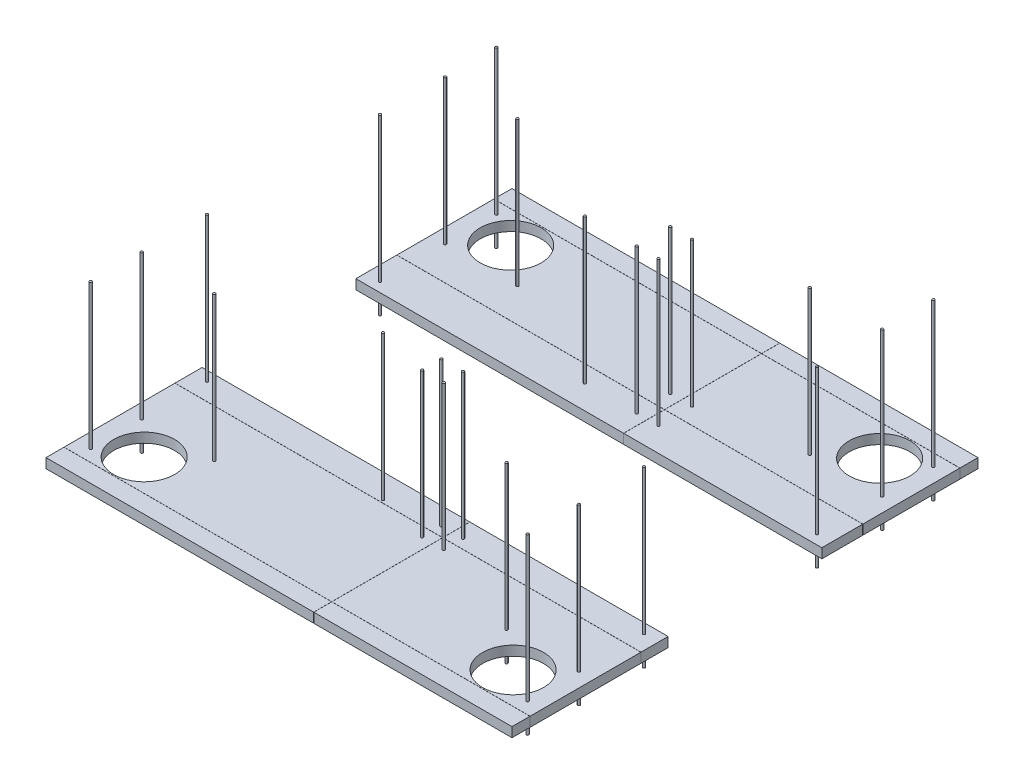
SolidWorks part; units mm, degrees
ref_plane "Front" through (0, 0, 0) normal (0, 0, 1) x (1, 0, 0)
ref_plane "Top" through (0, 0, 0) normal (0, 1, 0) x (1, 0, 0)
ref_plane "Right" through (0, 0, 0) normal (1, 0, 0) x (0, 0, -1)
sketch "Sketch1" plane through (0, 0, 0) normal (0, 1, 0) x (1, 0, 0)
  line L1 (-2454.275, 2454.275) -> (2454.275, 2454.275)
  line L2 (-2454.275, 2454.275) -> (-2454.275, -2454.275)
  line L3 (-2454.275, -2454.275) -> (2454.275, -2454.275)
  line L4 (2454.275, 2454.275) -> (2454.275, -2454.275)
  line L5 (-2454.275, 2454.275) -> (2454.275, -2454.275) construction
  line L6 (-2454.275, -2454.275) -> (2454.275, 2454.275) construction
  point P0 (0, 0)
  dimension "D1" = 4908.55
  dimension "D2" = 4908.55
extrude "Boss-Extrude1" add sketch "Sketch1" along normal blind 101.6
sketch "Sketch2" plane through (0, 101.6, 0) normal (0, 1, 0) x (1, 0, 0)
  line L0 (-2454.275, 2454.275) -> (-2454.275, -2454.275) construction
  line L1 (2454.275, -809.625) -> (-2454.275, -809.625)
  line L2 (2454.275, -809.625) -> (2454.275, 809.625)
  line L3 (2454.275, 809.625) -> (-2454.275, 809.625)
  line L4 (-2454.275, -809.625) -> (-2454.275, 809.625)
  line L5 (2454.275, -809.625) -> (-2454.275, 809.625) construction
  line L6 (2454.275, 809.625) -> (-2454.275, -809.625) construction
  point P0 (0, 0)
  dimension "D1" = 1619.25
extrude "Cut-Extrude1" cut sketch "Sketch2" against normal through all
sketch "Sketch4" plane through (0, 101.6, 0) normal (0, 1, 0) x (1, 0, 0)
  line L0 (-2454.275, -2263.775) -> (2454.275, -2263.775)
  line L3 (-2454.275, -2454.275) -> (2454.275, -2454.275) construction
  line L4 (-2454.275, -1095.375) -> (2454.275, -1095.375)
  line L5 (-2454.275, -809.625) -> (-2454.275, -2454.275) construction
  line L6 (-2454.275, -809.625) -> (2454.275, -809.625) construction
  line L7 (-2454.275, 2263.775) -> (2454.275, 2263.775)
  line L10 (-2454.275, 1241.425) -> (2454.275, 1241.425)
  line L11 (-2454.275, 2454.275) -> (-2454.275, 809.625) construction
  line L12 (2454.275, 809.625) -> (2454.275, 2454.275) construction
  line L13 (2454.275, 2454.275) -> (-2454.275, 2454.275) construction
  line L14 (2454.275, 809.625) -> (-2454.275, 809.625) construction
  line L15 (-2454.275, -1095.375) -> (-2454.275, -2263.775) construction
  line L16 (2454.275, -1095.375) -> (2454.275, -2263.775) construction
  line L17 (2454.275, 1241.425) -> (2454.275, 2263.775) construction
  line L18 (-2454.275, 1241.425) -> (-2454.275, 2263.775) construction
  line L19 (2454.275, -2454.275) -> (2454.275, -809.625) construction
  dimension "D1" = 190.5
  dimension "D2" = 1168.4
  dimension "D3" = 285.75
  dimension "D4" = 190.5
  dimension "D5" = 1022.35
  dimension "D6" = 431.8
extrude "Cut-Extrude-Thin1" cut sketch "Sketch4" against normal through all thin thin type one direction wall 1.27
sketch "Sketch5" plane through (0, 101.6, 0) normal (0, 1, 0) x (1, 0, 0)
  line L0 (365.125, -2454.275) -> (365.125, 2454.275)
  line L1 (-2454.275, -2454.275) -> (2454.275, -2454.275) construction
  line L2 (2454.275, 2454.275) -> (-2454.275, 2454.275) construction
  line L3 (2454.275, -2263.775) -> (2454.275, -1096.645) construction
  line L4 (-2454.275, -1096.645) -> (-2454.275, -2263.775) construction
  dimension "D1" = 2089.15
  dimension "D2" = 2819.4
extrude "Cut-Extrude-Thin2" cut sketch "Sketch5" against normal through all and the other way through all thin thin type one direction wall 1.27
sketch "Sketch8" plane through (0, 101.6, 0) normal (0, 1, 0) x (1, 0, 0)
  line L0 (-974.0807, 502.3386) -> (-974.0807, 1597.0052) construction
sketch "Sketch6" plane through (0, 101.6, 0) normal (0, 1, 0) x (1, 0, 0)
  line L0 (1943.1, 1929.13) -> (1943.1, 2262.505) construction
  line L1 (-1943.1, 1929.13) -> (1943.1, 1929.13) construction
  line L2 (-1943.1, 1929.13) -> (-1943.1, -1931.67) construction
  line L3 (-1943.1, -1931.67) -> (1943.1, -1931.67) construction
  line L4 (1943.1, 1929.13) -> (1943.1, -1931.67) construction
  line L5 (-1943.1, -1931.67) -> (-1943.1, -2265.045) construction
  line L6 (-2454.275, -2265.045) -> (365.125, -2265.045) construction
  line L7 (366.395, 2262.505) -> (2454.275, 2262.505) construction
  line L9 (2454.275, 1241.425) -> (2454.275, 2262.505) construction
  line L11 (-2454.275, -1096.645) -> (-2454.275, -2263.775) construction
  circle A0 centre (1943.1, 1929.13) radius 320.675
  circle A1 centre (-1943.1, 1929.13) radius 320.675
  circle A2 centre (-1943.1, -1931.67) radius 320.675
  circle A3 centre (1943.1, -1931.67) radius 320.675
  dimension "D1" = 641.35
  dimension "D3" = 190.5
  dimension "D4" = 190.5
  dimension "D2" = 12.7
extrude "DUCT HOLES" cut sketch "Sketch6" against normal through all
sketch "Sketch7" plane through (0, 101.6, 0) normal (0, 1, 0) x (1, 0, 0)
  line L0 (-1539.875, 2301.875) -> (-295.275, 2301.875) construction
  line L1 (-1539.875, 2301.875) -> (-2454.275, 2301.875) construction
  line L2 (-2454.275, 2454.275) -> (-2454.275, 2263.775) construction
  line L3 (365.125, 2454.275) -> (-2454.275, 2454.275) construction
  line L4 (-295.275, 2301.875) -> (365.125, 2301.875) construction
  line L5 (365.125, 2263.775) -> (365.125, 2454.275) construction
  line L6 (1539.875, 1597.025) -> (1539.875, 1063.625) construction
  line L7 (365.125, 2301.875) -> (974.725, 2301.875) construction
  line L8 (974.725, 2301.875) -> (1539.875, 2301.875) construction
  line L9 (1539.875, 2301.875) -> (2454.275, 2301.875) construction
  line L10 (2454.275, 2263.775) -> (2454.275, 2454.275) construction
  line L11 (366.395, 2263.775) -> (366.395, 2454.275) construction
  line L12 (2454.275, 1597.025) -> (-2454.275, 1597.025) construction
  line L13 (2454.275, 1241.425) -> (2454.275, 2262.505) construction
  line L14 (-2454.275, 2262.505) -> (-2454.275, 1241.425) construction
  line L15 (1539.875, 2301.875) -> (1539.875, 1597.025) construction
  line L16 (-2454.275, 1241.425) -> (365.125, 1241.425) construction
  line L17 (-295.275, 2301.875) -> (-295.275, 1597.025) construction
  line L18 (974.725, 2301.875) -> (974.725, 1597.025) construction
  line L19 (-2454.275, 2136.775) -> (2454.275, 2136.775) construction
  line L20 (-2454.275, 2263.775) -> (365.125, 2263.775) construction
  line L21 (-1539.875, 2301.875) -> (-1539.875, 2136.775) construction
  line L22 (-2454.275, 1063.625) -> (2454.275, 1063.625) construction
  line L23 (-2454.275, 1240.155) -> (-2454.275, 809.625) construction
  line L24 (2454.275, 809.625) -> (2454.275, 1240.155) construction
  line L25 (365.125, 809.625) -> (-2454.275, 809.625) construction
  line L26 (-1539.875, 1063.625) -> (-1539.875, 1597.025) construction
  line L27 (-295.275, 1597.025) -> (-295.275, 1063.625) construction
  line L28 (-2107.4102, -2022.1425) -> (-2107.4102, -819.4758) construction
  line L29 (-1539.875, 1285.875) -> (1539.875, 1285.875) construction
  line L30 (-2301.875, 1597.025) -> (-2301.875, 1063.625) construction
  line L31 (2301.875, 1597.025) -> (2301.875, 1063.625) construction
  line L32 (-2454.275, 1240.155) -> (365.125, 1240.155) construction
  line L33 (479.425, 1063.625) -> (250.825, 1063.625) construction
  line L34 (479.425, 1063.625) -> (479.425, 1416.685) construction
  line L35 (479.425, 1416.685) -> (250.825, 1416.685) construction
  line L36 (250.825, 1063.625) -> (250.825, 1416.685) construction
  line L37 (-2454.275, 1240.155) -> (365.125, 1240.155) construction
  line L38 (365.125, 809.625) -> (365.125, 1240.155) construction
  line L39 (365.125, 809.625) -> (365.125, 1240.155) construction
  line L40 (440.6472, 1241.425) -> (440.6472, 1063.625) construction
  line L41 (250.825, -1198.245) -> (479.425, -1198.245) construction
  line L42 (250.825, -1198.245) -> (250.825, -995.045) construction
  line L43 (250.825, -995.045) -> (479.425, -995.045) construction
  line L44 (479.425, -1198.245) -> (479.425, -995.045) construction
  line L45 (366.395, 1241.425) -> (2454.275, 1241.425) construction
  line L48 (-2454.275, -1096.645) -> (365.125, -1096.645) construction
  line L49 (-2454.275, -1096.645) -> (365.125, -1096.645) construction
  line L50 (-2301.875, 1063.625) -> (-2301.875, 911.225) construction
  line L51 (-2301.875, 911.225) -> (2301.875, 911.225) construction
  line L52 (2301.875, 911.225) -> (2301.875, 1063.625) construction
  circle A0 centre (-1539.875, 2301.875) radius 12.7 construction
  circle A4 centre (1539.875, 1597.025) radius 12.7
  circle A5 centre (-1539.875, 1597.025) radius 12.7
  circle A6 centre (479.425, 1063.625) radius 12.7
  circle A7 centre (-295.275, 1597.025) radius 12.7 construction
  circle A8 centre (974.725, 1597.025) radius 12.7 construction
  circle A9 centre (-295.275, 2136.775) radius 12.7 construction
  circle A10 centre (-1539.875, 2136.775) radius 12.7 construction
  circle A11 centre (974.725, 2136.775) radius 12.7 construction
  circle A12 centre (1539.875, 2136.775) radius 12.7 construction
  circle A13 centre (-295.275, 1063.625) radius 12.7
  circle A14 centre (-1539.875, 1063.625) radius 12.7 construction
  circle A15 centre (1539.875, 1063.625) radius 12.7 construction
  circle A16 centre (-2301.875, 1597.025) radius 12.7
  circle A17 centre (2301.875, 1597.025) radius 12.7
  circle A18 centre (-2301.875, 2136.775) radius 12.7
  circle A19 centre (2301.875, 2136.775) radius 12.7
  circle A20 centre (219.075, 2301.875) radius 12.7 construction
  circle A21 centre (658.495, 2301.875) radius 12.7 construction
  circle A22 centre (1539.875, 2301.875) radius 12.7 construction
  circle A23 centre (-650.875, 2301.875) radius 12.7 construction
  circle A24 centre (-1539.875, 1285.875) radius 12.7 construction
  circle A25 centre (1539.875, 1285.875) radius 12.7 construction
  circle A26 centre (-2301.875, 1063.625) radius 12.7 construction
  circle A27 centre (2301.875, 1063.625) radius 12.7 construction
  circle A28 centre (250.825, 1416.685) radius 12.7
  circle A29 centre (479.425, 1416.685) radius 12.7
  circle A30 centre (250.825, 1063.625) radius 12.7
  circle A31 centre (479.425, -995.045) radius 12.7
  circle A32 centre (250.825, -995.045) radius 12.7
  circle A33 centre (250.825, -1198.245) radius 12.7
  circle A34 centre (479.425, -1198.245) radius 12.7
  circle A35 centre (-2301.875, 911.225) radius 12.7
  circle A36 centre (2301.875, 911.225) radius 12.7
  point P107 (250.825, -1096.645)
  dimension "D1" = 25.4
  dimension "D5" = 609.6
  dimension "D7" = 355.6
  dimension "D11" = 152.4
  dimension "D14" = 152.4
  dimension "D19" = 889
  dimension "D20" = 914.4
  dimension "D21" = 1168.4
  dimension "D2" = 152.4
  dimension "D3" = 914.4
  dimension "D4" = 660.4
  dimension "D6" = 914.4
  dimension "D8" = 914.4
  dimension "D9" = 127
  dimension "D10" = 152.4
  dimension "D12" = 254
  dimension "D13" = 228.6
  dimension "D15" = 152.4
  dimension "D16" = 146.05
  dimension "D17" = 292.1
  dimension "D18" = 914.4
  dimension "D22" = 3079.75
  dimension "D23" = 203.2
  dimension "D24" = 152.4
extrude "UNISTRUT STUD LAYOUT" add sketch "Sketch7" along normal blind 1524 and the other way blind 304.8 separate body
mirror "Mirror3" about plane through (0, 0, 0) normal (0, 0, 1) of bodies 251 238 222 252 271 272 286 302 301 240 223 227 214 225 241 215 226 224 228 217 244 229 216 275 276 277 281 283 287 288 293 291 292
